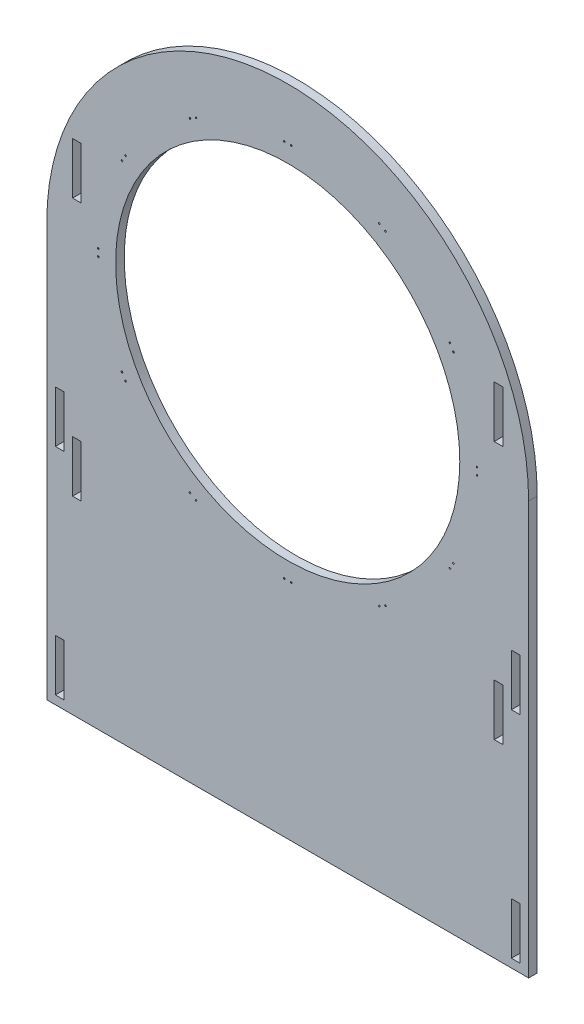
SolidWorks part; units mm, degrees
ref_plane "Front Plane" through (0, 0, 0) normal (0, 0, 1) x (1, 0, 0)
ref_plane "Top Plane" through (0, 0, 0) normal (0, 1, 0) x (1, 0, 0)
ref_plane "Right Plane" through (0, 0, 0) normal (1, 0, 0) x (0, 0, -1)
sketch "Sketch1" plane through (0, 0, 0) normal (0, 0, 1) x (1, 0, 0)
  line L0 (-88.9, 0) -> (-88.9, -152.4)
  line L1 (-88.9, -152.4) -> (88.9, -152.4)
  line L2 (88.9, -152.4) -> (88.9, 0)
  line L3 (0, 63.5) -> (0, 69.85) construction
  line L4 (1.3017, 69.85) -> (-1.3017, 69.85) construction
  line L5 (1.5684, 69.5833) -> (1.035, 70.1167) construction
  line L6 (-1.5684, 70.1167) -> (-1.035, 70.1167)
  line L7 (-1.5684, 70.1167) -> (-1.5684, 69.5833)
  line L8 (-1.5684, 69.5833) -> (-1.035, 69.5833)
  line L9 (-1.035, 70.1167) -> (-1.035, 69.5833)
  line L10 (-1.5684, 70.1167) -> (-1.035, 69.5833) construction
  line L11 (-1.5684, 69.5833) -> (-1.035, 70.1167) construction
  line L12 (1.5684, 70.1167) -> (1.035, 69.5833) construction
  line L13 (1.035, 70.1167) -> (1.035, 69.5833)
  line L14 (1.5684, 69.5833) -> (1.035, 69.5833)
  line L15 (1.5684, 70.1167) -> (1.5684, 69.5833)
  line L16 (1.5684, 70.1167) -> (1.035, 70.1167)
  line L17 (33.7, 61.5071) -> (34.162, 61.2404)
  line L18 (33.7, 61.5071) -> (33.4333, 61.0451)
  line L19 (33.4333, 61.0451) -> (33.8953, 60.7784)
  line L20 (34.162, 61.2404) -> (33.8953, 60.7784)
  line L21 (35.9547, 60.2053) -> (35.688, 59.7434)
  line L22 (36.15, 59.4767) -> (35.688, 59.7434)
  line L23 (36.4167, 59.9386) -> (36.15, 59.4767)
  line L24 (36.4167, 59.9386) -> (35.9547, 60.2053)
  line L25 (36.15, 59.4767) -> (35.9547, 60.2053) construction
  line L26 (33.7, 61.5071) -> (33.8953, 60.7784) construction
  line L27 (33.4333, 61.0451) -> (34.162, 61.2404) construction
  line L28 (36.4167, 59.9386) -> (35.688, 59.7434) construction
  line L29 (59.9386, 36.4167) -> (60.2053, 35.9547)
  line L30 (59.9386, 36.4167) -> (59.4767, 36.15)
  line L31 (59.4767, 36.15) -> (59.7434, 35.688)
  line L32 (60.2053, 35.9547) -> (59.7434, 35.688)
  line L33 (61.2404, 34.162) -> (60.7784, 33.8953)
  line L34 (61.0451, 33.4333) -> (60.7784, 33.8953)
  line L35 (61.5071, 33.7) -> (61.0451, 33.4333)
  line L36 (61.5071, 33.7) -> (61.2404, 34.162)
  line L37 (61.0451, 33.4333) -> (61.2404, 34.162) construction
  line L38 (59.9386, 36.4167) -> (59.7434, 35.688) construction
  line L39 (59.4767, 36.15) -> (60.2053, 35.9547) construction
  line L40 (61.5071, 33.7) -> (60.7784, 33.8953) construction
  line L41 (70.1167, 1.5685) -> (70.1167, 1.0351)
  line L42 (70.1167, 1.5685) -> (69.5833, 1.5685)
  line L43 (69.5833, 1.5685) -> (69.5833, 1.0351)
  line L44 (70.1167, 1.0351) -> (69.5833, 1.0351)
  line L45 (70.1167, -1.035) -> (69.5833, -1.035)
  line L46 (69.5833, -1.5684) -> (69.5833, -1.035)
  line L47 (70.1167, -1.5684) -> (69.5833, -1.5684)
  line L48 (70.1167, -1.5684) -> (70.1167, -1.035)
  line L49 (69.5833, -1.5684) -> (70.1167, -1.035) construction
  line L50 (70.1167, 1.5685) -> (69.5833, 1.0351) construction
  line L51 (69.5833, 1.5685) -> (70.1167, 1.0351) construction
  line L52 (70.1167, -1.5684) -> (69.5833, -1.035) construction
  line L53 (61.5071, -33.7) -> (61.2404, -34.162)
  line L54 (61.5071, -33.7) -> (61.0451, -33.4333)
  line L55 (61.0451, -33.4333) -> (60.7784, -33.8953)
  line L56 (61.2404, -34.162) -> (60.7784, -33.8953)
  line L57 (60.2053, -35.9547) -> (59.7434, -35.688)
  line L58 (59.4767, -36.15) -> (59.7434, -35.688)
  line L59 (59.9386, -36.4167) -> (59.4767, -36.15)
  line L60 (59.9386, -36.4167) -> (60.2053, -35.9547)
  line L61 (59.4767, -36.15) -> (60.2053, -35.9547) construction
  line L62 (61.5071, -33.7) -> (60.7784, -33.8953) construction
  line L63 (61.0451, -33.4333) -> (61.2404, -34.162) construction
  line L64 (59.9386, -36.4167) -> (59.7434, -35.688) construction
  line L65 (36.4167, -59.9386) -> (35.9547, -60.2053)
  line L66 (36.4167, -59.9386) -> (36.15, -59.4767)
  line L67 (36.15, -59.4767) -> (35.688, -59.7434)
  line L68 (35.9547, -60.2053) -> (35.688, -59.7434)
  line L69 (34.162, -61.2404) -> (33.8953, -60.7784)
  line L70 (33.4333, -61.0451) -> (33.8953, -60.7784)
  line L71 (33.7, -61.5071) -> (33.4333, -61.0451)
  line L72 (33.7, -61.5071) -> (34.162, -61.2404)
  line L73 (33.4333, -61.0451) -> (34.162, -61.2404) construction
  line L74 (36.4167, -59.9386) -> (35.688, -59.7434) construction
  line L75 (36.15, -59.4767) -> (35.9547, -60.2053) construction
  line L76 (33.7, -61.5071) -> (33.8953, -60.7784) construction
  line L77 (1.5685, -70.1167) -> (1.0351, -70.1167)
  line L78 (1.5685, -70.1167) -> (1.5685, -69.5833)
  line L79 (1.5685, -69.5833) -> (1.0351, -69.5833)
  line L80 (1.0351, -70.1167) -> (1.0351, -69.5833)
  line L81 (-1.035, -70.1167) -> (-1.035, -69.5833)
  line L82 (-1.5684, -69.5833) -> (-1.035, -69.5833)
  line L83 (-1.5684, -70.1167) -> (-1.5684, -69.5833)
  line L84 (-1.5684, -70.1167) -> (-1.035, -70.1167)
  line L85 (-1.5684, -69.5833) -> (-1.035, -70.1167) construction
  line L86 (1.5685, -70.1167) -> (1.0351, -69.5833) construction
  line L87 (1.5685, -69.5833) -> (1.0351, -70.1167) construction
  line L88 (-1.5684, -70.1167) -> (-1.035, -69.5833) construction
  line L89 (-33.7, -61.5071) -> (-34.162, -61.2404)
  line L90 (-33.7, -61.5071) -> (-33.4333, -61.0451)
  line L91 (-33.4333, -61.0451) -> (-33.8953, -60.7784)
  line L92 (-34.162, -61.2404) -> (-33.8953, -60.7784)
  line L93 (-35.9547, -60.2053) -> (-35.688, -59.7434)
  line L94 (-36.15, -59.4767) -> (-35.688, -59.7434)
  line L95 (-36.4167, -59.9386) -> (-36.15, -59.4767)
  line L96 (-36.4167, -59.9386) -> (-35.9547, -60.2053)
  line L97 (-36.15, -59.4767) -> (-35.9547, -60.2053) construction
  line L98 (-33.7, -61.5071) -> (-33.8953, -60.7784) construction
  line L99 (-33.4333, -61.0451) -> (-34.162, -61.2404) construction
  line L100 (-36.4167, -59.9386) -> (-35.688, -59.7434) construction
  line L101 (-59.9386, -36.4167) -> (-60.2053, -35.9547)
  line L102 (-59.9386, -36.4167) -> (-59.4767, -36.15)
  line L103 (-59.4767, -36.15) -> (-59.7434, -35.688)
  line L104 (-60.2053, -35.9547) -> (-59.7434, -35.688)
  line L105 (-61.2404, -34.162) -> (-60.7784, -33.8953)
  line L106 (-61.0451, -33.4333) -> (-60.7784, -33.8953)
  line L107 (-61.5071, -33.7) -> (-61.0451, -33.4333)
  line L108 (-61.5071, -33.7) -> (-61.2404, -34.162)
  line L109 (-61.0451, -33.4333) -> (-61.2404, -34.162) construction
  line L110 (-59.9386, -36.4167) -> (-59.7434, -35.688) construction
  line L111 (-59.4767, -36.15) -> (-60.2053, -35.9547) construction
  line L112 (-61.5071, -33.7) -> (-60.7784, -33.8953) construction
  line L113 (-70.1167, -1.5685) -> (-70.1167, -1.0351)
  line L114 (-70.1167, -1.5685) -> (-69.5833, -1.5685)
  line L115 (-69.5833, -1.5685) -> (-69.5833, -1.0351)
  line L116 (-70.1167, -1.0351) -> (-69.5833, -1.0351)
  line L117 (-70.1167, 1.035) -> (-69.5833, 1.035)
  line L118 (-69.5833, 1.5684) -> (-69.5833, 1.035)
  line L119 (-70.1167, 1.5684) -> (-69.5833, 1.5684)
  line L120 (-70.1167, 1.5684) -> (-70.1167, 1.035)
  line L121 (-69.5833, 1.5684) -> (-70.1167, 1.035) construction
  line L122 (-70.1167, -1.5685) -> (-69.5833, -1.0351) construction
  line L123 (-69.5833, -1.5685) -> (-70.1167, -1.0351) construction
  line L124 (-70.1167, 1.5684) -> (-69.5833, 1.035) construction
  line L125 (-61.5071, 33.7) -> (-61.2404, 34.162)
  line L126 (-61.5071, 33.7) -> (-61.0451, 33.4333)
  line L127 (-61.0451, 33.4333) -> (-60.7784, 33.8953)
  line L128 (-61.2404, 34.162) -> (-60.7784, 33.8953)
  line L129 (-60.2053, 35.9547) -> (-59.7434, 35.688)
  line L130 (-59.4767, 36.15) -> (-59.7434, 35.688)
  line L131 (-59.9386, 36.4167) -> (-59.4767, 36.15)
  line L132 (-59.9386, 36.4167) -> (-60.2053, 35.9547)
  line L133 (-59.4767, 36.15) -> (-60.2053, 35.9547) construction
  line L134 (-61.5071, 33.7) -> (-60.7784, 33.8953) construction
  line L135 (-61.0451, 33.4333) -> (-61.2404, 34.162) construction
  line L136 (-59.9386, 36.4167) -> (-59.7434, 35.688) construction
  line L137 (-36.4167, 59.9386) -> (-35.9547, 60.2053)
  line L138 (-36.4167, 59.9386) -> (-36.15, 59.4767)
  line L139 (-36.15, 59.4767) -> (-35.688, 59.7434)
  line L140 (-35.9547, 60.2053) -> (-35.688, 59.7434)
  line L141 (-34.162, 61.2404) -> (-33.8953, 60.7784)
  line L142 (-33.4333, 61.0451) -> (-33.8953, 60.7784)
  line L143 (-33.7, 61.5071) -> (-33.4333, 61.0451)
  line L144 (-33.7, 61.5071) -> (-34.162, 61.2404)
  line L145 (-33.4333, 61.0451) -> (-34.162, 61.2404) construction
  line L146 (-36.4167, 59.9386) -> (-35.688, 59.7434) construction
  line L147 (-36.15, 59.4767) -> (-35.9547, 60.2053) construction
  line L148 (-33.7, 61.5071) -> (-33.8953, 60.7784) construction
  line L149 (-79.375, 31.7348) -> (-76.2, 31.7348) construction
  line L150 (-76.2, 31.7348) -> (-79.375, 31.7348)
  line L151 (-76.2, 31.7348) -> (-76.2, 12.6848)
  line L152 (-76.2, 12.6848) -> (-79.375, 12.6848)
  line L153 (-79.375, 31.7348) -> (-79.375, 12.6848)
  line L154 (-76.2, 31.7348) -> (-76.2, 12.6848) construction
  line L155 (0, -152.4) -> (0, 0) construction
  line L156 (-76.2, -63.5152) -> (-79.375, -63.5152)
  line L157 (-76.2, -63.5152) -> (-76.2, -82.5652)
  line L158 (-76.2, -82.5652) -> (-79.375, -82.5652)
  line L159 (-79.375, -63.5152) -> (-79.375, -82.5652)
  line L160 (-82.55, -130.2134) -> (-85.725, -130.2134)
  line L161 (-82.55, -130.2134) -> (-82.55, -149.2634)
  line L162 (-82.55, -149.2634) -> (-85.725, -149.2634)
  line L163 (-85.725, -130.2134) -> (-85.725, -149.2634)
  line L164 (-82.55, -50.8) -> (-85.725, -50.8)
  line L165 (-82.55, -50.8) -> (-82.55, -69.85)
  line L166 (-82.55, -69.85) -> (-85.725, -69.85)
  line L167 (-85.725, -50.8) -> (-85.725, -69.85)
  line L168 (85.725, -130.2134) -> (85.725, -149.2634)
  line L169 (82.55, -149.2634) -> (85.725, -149.2634)
  line L170 (82.55, -130.2134) -> (82.55, -149.2634)
  line L171 (82.55, -130.2134) -> (85.725, -130.2134)
  line L172 (79.375, 31.7348) -> (79.375, 12.6848)
  line L173 (76.2, 12.6848) -> (79.375, 12.6848)
  line L174 (76.2, 31.7348) -> (76.2, 12.6848)
  line L175 (76.2, 31.7348) -> (79.375, 31.7348)
  line L176 (85.725, -50.8) -> (85.725, -69.85)
  line L177 (82.55, -69.85) -> (85.725, -69.85)
  line L178 (82.55, -50.8) -> (82.55, -69.85)
  line L179 (82.55, -50.8) -> (85.725, -50.8)
  line L180 (79.375, -63.5152) -> (79.375, -82.5652)
  line L181 (76.2, -82.5652) -> (79.375, -82.5652)
  line L182 (76.2, -63.5152) -> (76.2, -82.5652)
  line L183 (76.2, -63.5152) -> (79.375, -63.5152)
  circle A0 centre (0, 0) radius 63.5
  arc A2 (88.9, 0) -> (-88.9, 0) centre (0, 0) ccw
  point P11 (0, 69.85)
  dimension "D1" = 127
  dimension "D2" = 88.9
  dimension "D7" = 0.5334
  dimension "D3" = 177.8
  dimension "D4" = 152.4
  dimension "D5" = 6.35
  dimension "D6" = 2.6035
extrude "Boss-Extrude1" add sketch "Sketch1" along normal blind 3.175
ref_plane "Plane1" through (88.9, -152.4, 0) normal (1, 0, 0) x (0, 0, -1)
